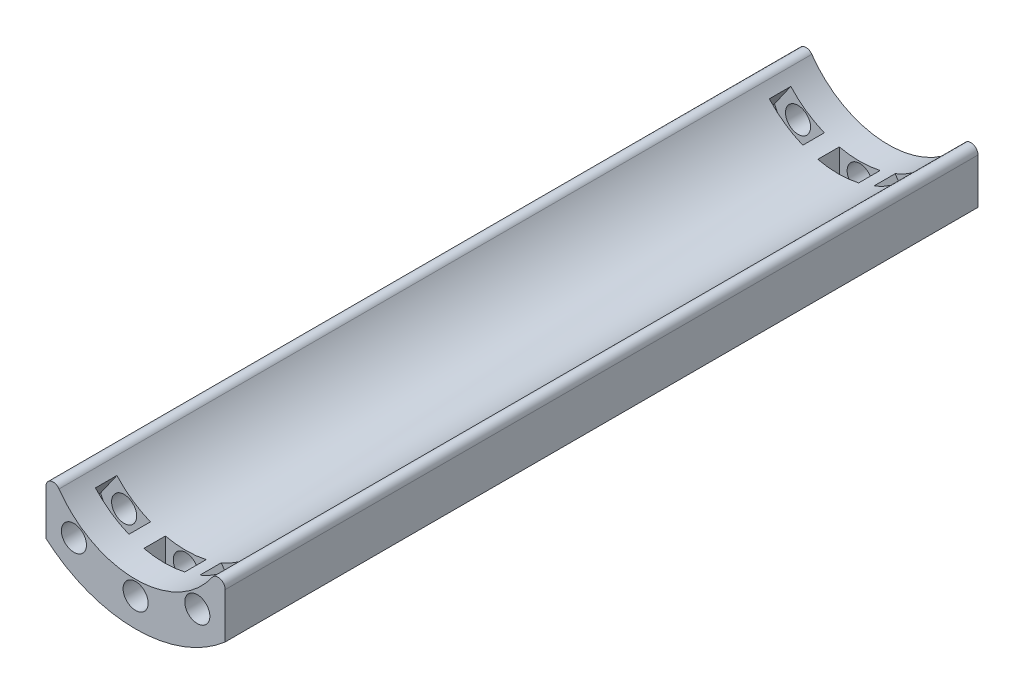
SolidWorks part; units mm, degrees
ref_plane "Front Plane" through (0, 0, 0) normal (0, 0, 1) x (1, 0, 0)
ref_plane "Top Plane" through (0, 0, 0) normal (0, 1, 0) x (1, 0, 0)
ref_plane "Right Plane" through (0, 0, 0) normal (1, 0, 0) x (0, 0, -1)
sketch "Sketch1" plane through (0, 0, 0) normal (0, 0, 1) x (1, 0, 0)
  line L2 (-18.375, -14.3091) -> (-18.375, 161.3091)
  line L3 (-43.375, 161.3091) -> (-43.375, -14.3091)
  line L4 (-18.375, -14.3091) -> (-18.375, 161.3091)
  line L5 (-43.375, 161.3091) -> (-43.375, -14.3091)
  circle A0 centre (-30.875, 0) radius 13
  arc A2 (-18.375, 161.3091) -> (-43.375, 161.3091) centre (-30.875, 147) ccw
  arc A3 (-43.375, -14.3091) -> (-18.375, -14.3091) centre (-30.875, 0) ccw
  arc A4 (-18.375, 161.3091) -> (-43.375, 161.3091) centre (-30.875, 147) ccw
  arc A5 (-43.375, -14.3091) -> (-18.375, -14.3091) centre (-30.875, 0) ccw
  dimension "D2" = 6
  dimension "D1" = 0
extrude "Boss-Extrude1" add sketch "Sketch1" along normal up to surface (105 mm away) contours L5 A5 L4 A0 region at (-30.875, -13.7148, 0)
sketch "Sketch3" plane through (0, 0, 0) normal (0, 0, -1) x (-1, 0, 0)
  circle A1 centre (30.875, -15) radius 1.75 construction
  circle A2 centre (39.4786, -12.2873) radius 1.75 construction
  circle A3 centre (22.2714, -12.2873) radius 1.75
  circle A4 centre (30.875, -15) radius 1.75
  circle A5 centre (39.4786, -12.2873) radius 1.75
  circle A6 centre (22.2714, -12.2873) radius 1.75 construction
  circle A7 centre (22.2714, -12.2873) radius 1.75 construction
extrude "Cut-Extrude1" cut sketch "Sketch3" against normal blind 15 contours A3 | A4 | A5 region at (-22.2714, -12.2873, 0) region at (-30.875, -15, 0) region at (-39.4786, -12.2873, 0)
ref_plane "Plane1" through (0, 0, 4) normal (0, 0, -1) x (-1, 0, 0)
ref_plane "Plane2" through (0, 0, 52.5) normal (0, 0, -1) x (-1, 0, 0)
sketch "Sketch4" plane through (0, 0, 4) normal (0, 0, -1) x (-1, 0, 0)
  line L0 (20.8806, -9.3047) -> (21.2653, -8.7552)
  line L1 (30.875, -18.2909) -> (33.725, -16.6454)
  line L2 (33.725, -16.6454) -> (33.725, -13.3546)
  line L3 (33.725, -13.3546) -> (30.875, -11.7091)
  line L4 (30.875, -11.7091) -> (28.025, -13.3546)
  line L5 (28.025, -13.3546) -> (28.025, -16.6454)
  line L6 (28.025, -16.6454) -> (30.875, -18.2909)
  line L7 (25.5497, -12.5741) -> (25.9345, -12.0246)
  line L8 (24.1589, -9.5915) -> (20.3838, -14.983) construction
  line L9 (20.3838, -14.983) -> (23.6621, -15.2698)
  line L10 (23.6621, -15.2698) -> (25.5497, -12.5741)
  line L11 (25.5497, -12.5741) -> (24.1589, -9.5915)
  line L12 (24.1589, -9.5915) -> (20.8806, -9.3047)
  line L13 (20.8806, -9.3047) -> (18.993, -12.0005)
  line L14 (18.993, -12.0005) -> (20.3838, -14.983)
  line L15 (30.875, 0) -> (24.1589, -9.5915) construction
  line L16 (30.875, 0) -> (30.875, -19) construction
  line L17 (28.025, -13.3546) -> (28.025, -12.6837)
  line L18 (33.725, -13.3546) -> (33.725, -12.6837)
  line L19 (36.2003, -12.5741) -> (37.5911, -9.5915)
  line L20 (37.5911, -9.5915) -> (40.8694, -9.3047)
  line L21 (40.8694, -9.3047) -> (42.757, -12.0005)
  line L22 (42.757, -12.0005) -> (41.3662, -14.983)
  line L23 (41.3662, -14.983) -> (38.0879, -15.2698)
  line L24 (38.0879, -15.2698) -> (36.2003, -12.5741)
  line L25 (36.2003, -12.5741) -> (35.8155, -12.0246)
  line L26 (40.8694, -9.3047) -> (40.4847, -8.7552)
  line L27 (18.375, -14.3091) -> (18.375, -3.5707) construction
  line L28 (18.375, -14.3091) -> (18.375, -3.5707)
  line L29 (43.375, -3.5707) -> (43.375, -14.3091) construction
  line L30 (43.375, -3.5707) -> (43.375, -14.3091)
  circle A0 centre (30.875, -15) radius 2.85 construction
  arc A1 (18.375, -14.3091) -> (43.375, -14.3091) centre (30.875, 0) ccw construction
  arc A2 (18.375, -14.3091) -> (43.375, -14.3091) centre (30.875, 0) ccw
  arc A3 (18.375, -3.5707) -> (43.375, -3.5707) centre (30.875, 0) ccw construction
  arc A4 (18.375, -3.5707) -> (43.375, -3.5707) centre (30.875, 0) ccw
  circle A5 centre (22.2714, -12.2873) radius 2.85 construction
  circle A6 centre (22.2714, -12.2873) radius 1.75 construction
  circle A7 centre (30.875, -15) radius 1.75 construction
  dimension "D1" = 5.7
extrude "Cut-Extrude2" cut sketch "Sketch4" against normal blind 3 contours A4 L12 L13 L14 A2 L9 L10 L11 | A4 L0 L12 | A4 L11 L7 | A4 L4 L5 L6 A2 L1 L2 L3 | A4 L17 L4 | A4 L3 L18 | A4 L19 L24 L23 A2 L22 L21 L20 | A4 L25 L19 | A4 L20 L26 region at (-21.3409, -9.1521, 4) region at (-22.1244, -12.4971, 4) region at (-25.5357, -12.0894, 4) region at (-28.3145, -12.9655, 4) region at (-30.875, -15.2561, 4) region at (-40.4091, -9.1521, 4) region at (-33.4355, -12.9655, 4) region at (-39.6256, -12.4971, 4) region at (-36.2143, -12.0894, 4)
mirror "Mirror1" about plane through (0, 0, 52.5) normal (0, 0, -1) of "Cut-Extrude1", "Cut-Extrude2"
fillet "Fillet1" radius 1 2 edges at (-43.375, -3.5707, 52.5) (-18.375, -3.5707, 52.5)
ref_plane "Plane3" through (0, -19, 0) normal (0, -1, 0) x (-1, 0, 0)
